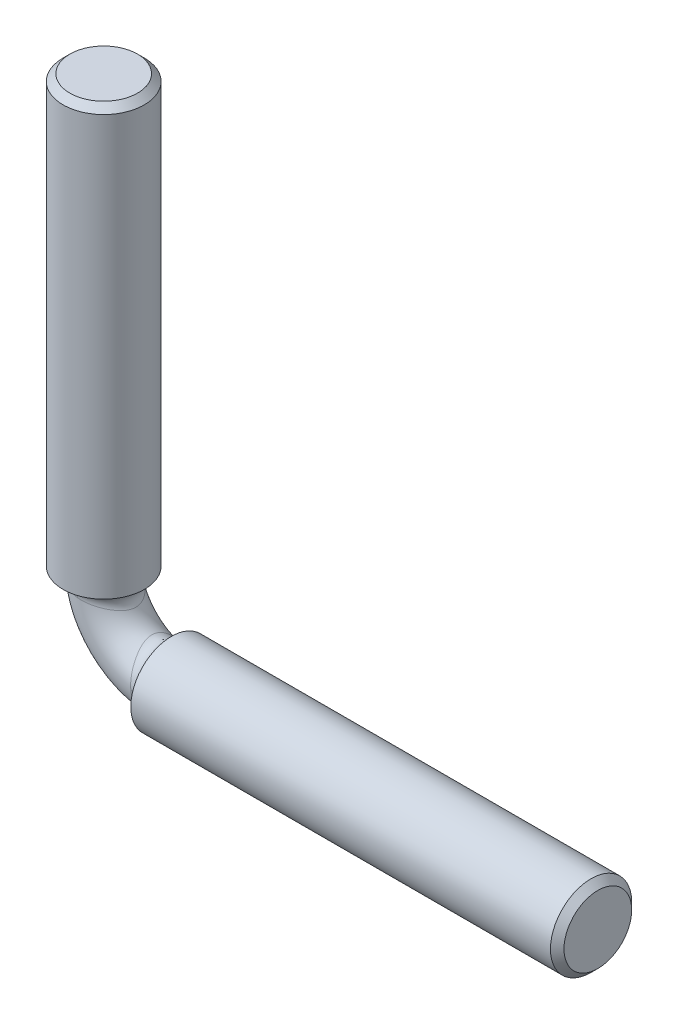
SolidWorks part; units mm, degrees
ref_plane "Front Plane" through (0, 0, 0) normal (0, 0, 1) x (1, 0, 0)
ref_plane "Top Plane" through (0, 0, 0) normal (0, 1, 0) x (1, 0, 0)
ref_plane "Right Plane" through (0, 0, 0) normal (1, 0, 0) x (0, 0, -1)
sketch "Sketch1" plane through (0, 0, 0) normal (0, 0, 1) x (1, 0, 0)
  line L0 (0, 31.5) -> (0, 0)
  line L1 (5, -5) -> (36.5, -5)
  arc A0 (0, 0) -> (5, -5) centre (5, 0) ccw
  point P4 (0, 0)
  dimension "D1" = 5
  dimension "D2" = 31.5
  dimension "D3" = 31.5
other "AlignGroup1"
sweep "Sweep1" add path "Sketch1" circular profile diameter 4 parameters "D3"=4
sketch "Sketch9" plane through (0, 31.5, 0) normal (0, 1, 0) x (1, 0, 0)
  circle A0 centre (0, 0) radius 3
  dimension "D1" = 6
extrude "Boss-Extrude1" add sketch "Sketch9" against normal blind 31.5
sketch "Sketch10" plane through (36.5, 0, 0) normal (1, 0, 0) x (0, 0, -1)
  circle A0 centre (0, -5) radius 3
  dimension "D1" = 6
extrude "Boss-Extrude2" add sketch "Sketch10" against normal blind 31.5
chamfer "Chamfer1" distance 0.5 angle 45 2 edges at (36.5, -5, -3) (-3, 31.5, 0)
fillet "Fillet1" radius 1 2 edges at (0, 0, 2) (5, -5, -2)
